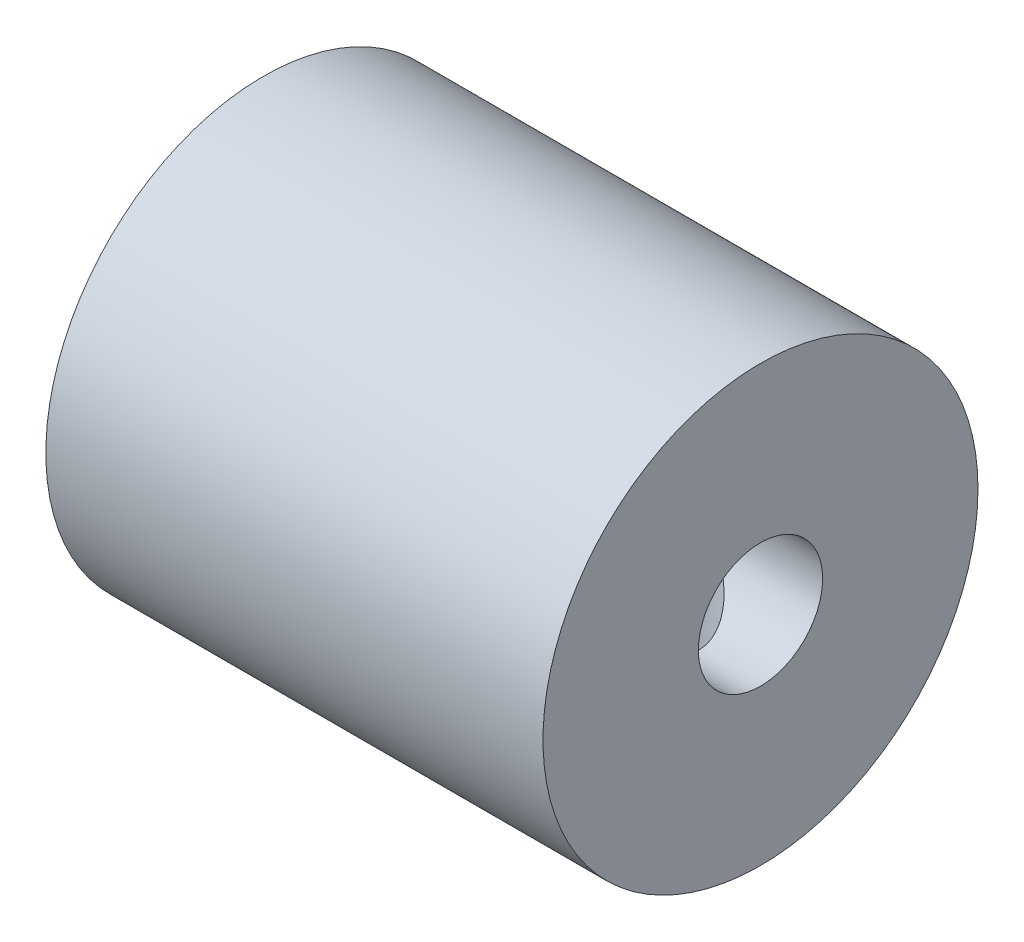
SolidWorks part; units mm, degrees
ref_plane "Front Plane" through (0, 0, 0) normal (0, 0, 1) x (1, 0, 0)
ref_plane "Top Plane" through (0, 0, 0) normal (0, 1, 0) x (1, 0, 0)
ref_plane "Right Plane" through (0, 0, 0) normal (1, 0, 0) x (0, 0, -1)
sketch "Sketch1" plane through (0, 0, 0) normal (0, 0, 1) x (1, 0, 0)
  line L0 (-12.7, 11.1125) -> (-12.7, 0)
  line L1 (-12.7, 0) -> (12.7, 0)
  line L2 (12.7, 0) -> (12.7, 11.1125)
  line L3 (12.7, 11.1125) -> (-12.7, 11.1125)
  line L4 (-12.7, 0) -> (12.7, 0) construction
revolve "Revolve1" add sketch "Sketch1" angle 360 about L4 reverse direction yes
hole_wizard "Hole1" positions "Sketch3" profile "Sketch2" legacy
sketch "Sketch3" plane through (-12.7, 0, 0) normal (-1, 0, 0) x (0, 0, 1)
  point P0 (0, 0)
sketch "Sketch2" plane through (-12.7, 0, 0) normal (0, 1, 0) x (0, 0, 1)
  line L0 (0, 0) -> (0, 25.4)
  line L1 (0, 25.4) -> (3.175, 25.4)
  line L2 (3.175, 25.4) -> (3.175, 12.7)
  line L3 (3.175, 12.7) -> (5.5563, 12.7)
  line L4 (5.5563, 12.7) -> (5.5563, 0)
  line L5 (5.5563, 0) -> (0, 0)
  line L6 (0, 110) -> (0, -10) construction
  dimension "Diameter" = 6.35
  dimension "Depth" = 25.4
  dimension "C-Bore Diameter" = 11.1125
  dimension "C-Bore Depth" = 12.7
ref_plane "Plane1" through (0, 0, 0) normal (0, 1, 0) x (1, 0, 0)
hole_wizard "Hole2" positions "Sketch5" profile "Sketch4" legacy
sketch "Sketch5" plane through (0, 0, 0) normal (0, 1, 0) x (1, 0, 0)
  point P0 (6.35, 0)
sketch "Sketch4" plane through (6.35, 0, 0) normal (1, 0, 0) x (0, 0, 1)
  line L0 (0, 0) -> (0, 11.1125)
  line L1 (0, 11.1125) -> (3.175, 11.1125)
  line L2 (3.175, 11.1125) -> (3.175, 0)
  line L3 (3.175, 0) -> (0, 0)
  line L4 (0, 110) -> (0, -10) construction
  dimension "Diameter" = 6.35
  dimension "Depth" = 11.1125
ref_plane "Plane2" through (0, -4.5597, 0) normal (0, 1, 0) x (1, 0, 0)
hole_wizard "Hole3" positions "Sketch7" profile "Sketch6" legacy
sketch "Sketch7" plane through (0, -4.5597, 0) normal (0, 1, 0) x (1, 0, 0)
  point P0 (-6.35, 0)
sketch "Sketch6" plane through (-6.35, -4.5597, 0) normal (1, 0, 0) x (0, 0, 1)
  line L0 (0, 0) -> (0, 6.5528)
  line L1 (0, 6.5528) -> (3.175, 6.5528)
  line L2 (3.175, 6.5528) -> (3.175, 0)
  line L3 (3.175, 0) -> (0, 0)
  line L4 (0, 110) -> (0, -10) construction
  dimension "Diameter" = 6.35
  dimension "Depth" = 6.5528
ref_axis "Axis1" through (6.35, -11.1125, 0) along (0, 1, 0)
